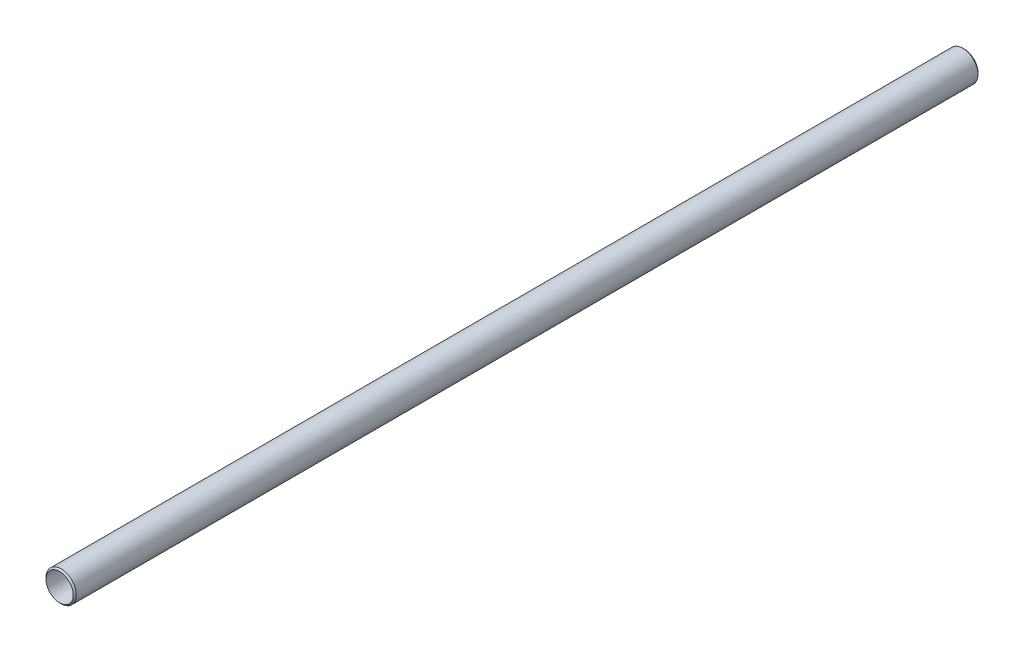
SolidWorks part; units mm, degrees
material "1.7005 (45Cr2)"
ref_plane "Płaszczyzna przednia" through (0, 0, 0) normal (0, 0, 1) x (1, 0, 0)
ref_plane "Płaszczyzna górna" through (0, 0, 0) normal (0, 1, 0) x (1, 0, 0)
ref_plane "Płaszczyzna prawa" through (0, 0, 0) normal (1, 0, 0) x (0, 0, -1)
sketch "Szkic1" plane through (0, 0, 0) normal (0, 0, 1) x (1, 0, 0)
  circle A0 centre (0, 0) radius 5
  circle A1 centre (0, 0) radius 4.5
  dimension "D1" = 0.5
extrude "Dodanie-wyciągnięcie1" add sketch "Szkic1" along normal blind 300
chamfer "Sfazowanie1" distance 1 angle 45 2 edges at (5, 0, 0) (5, 0, 300)
